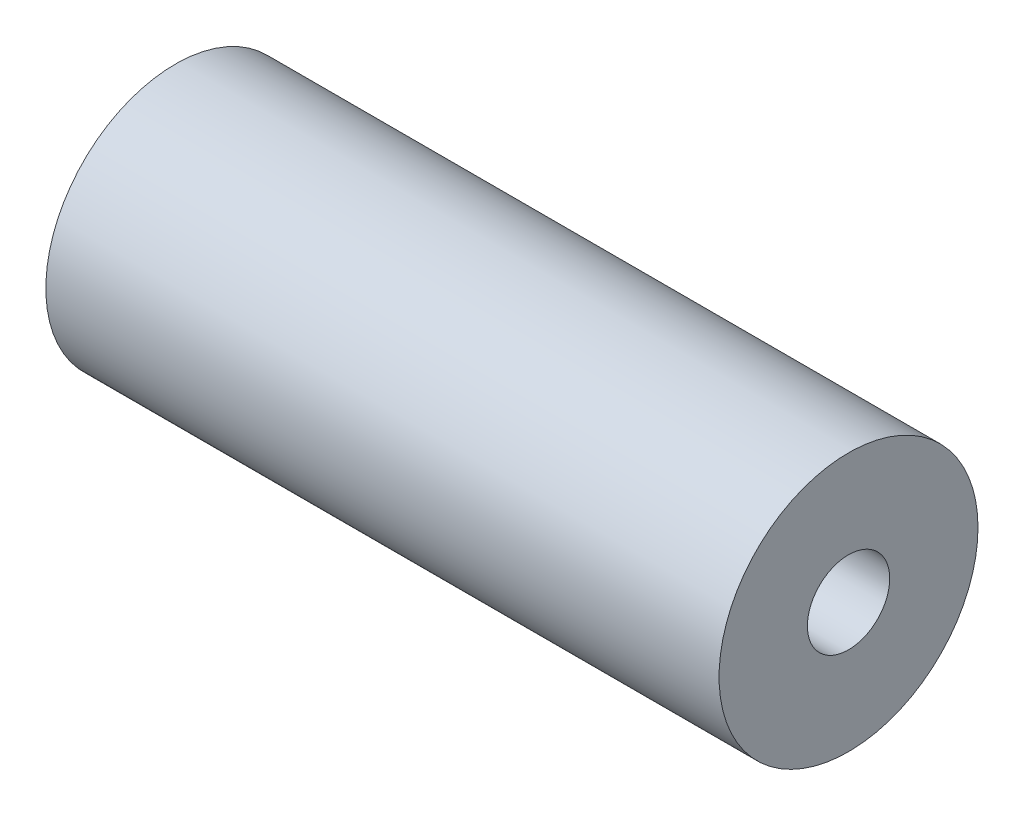
SolidWorks part; units mm, degrees
material "6061-T6 (SS)"
ref_plane "Front Plane" through (0, 0, 0) normal (0, 0, 1) x (1, 0, 0)
ref_plane "Top Plane" through (0, 0, 0) normal (0, 1, 0) x (1, 0, 0)
ref_plane "Right Plane" through (0, 0, 0) normal (1, 0, 0) x (0, 0, -1)
sketch "Sketch1" plane through (0, 0, 0) normal (1, 0, 0) x (0, 0, -1)
  circle A0 centre (0, 0) radius 6.35
  dimension "D1" = 12.7
extrude "Boss-Extrude1" add sketch "Sketch1" along normal mid plane 33.02
hole_wizard "Tap Drill for #10-32 Tap1" positions "Sketch2" profile "Sketch3" hole size "#10-32" standard "ANSI Inch"
sketch "Sketch2" plane through (16.51, 0, 0) normal (1, 0, 0) x (0, 0, -1)
  point P0 (0, 0)
sketch "Sketch3" plane through (16.51, 0, 0) normal (0, 1, 0) x (0, 0, -1)
  line L0 (0, 0) -> (0, 11.3733)
  line L1 (0, 11.3733) -> (2.0193, 10.16)
  line L2 (2.0193, 10.16) -> (2.0193, 0)
  line L5 (2.0193, 0) -> (0, 0)
  line L10 (0, 11.3733) -> (-2.0193, 10.16) construction
  line L11 (0, -6.35) -> (0, 107.95) construction
  dimension "Hole Dia." = 4.0386
  dimension "Hole Depth" = 10.16
  dimension "Drill Angle" = 118
mirror "Mirror1" about plane through (0, 0, 0) normal (1, 0, 0) of "Tap Drill for #10-32 Tap1"
